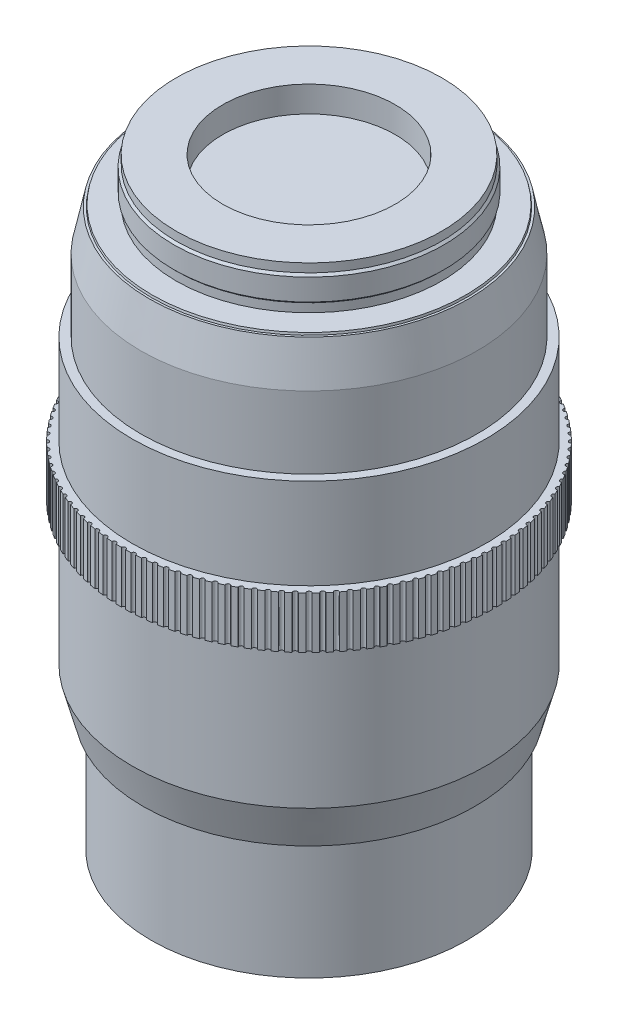
SolidWorks part; units mm, degrees
ref_plane "Front Plane" through (0, 0, 0) normal (0, 0, 1) x (1, 0, 0)
ref_plane "Top Plane" through (0, 0, 0) normal (0, 1, 0) x (1, 0, 0)
ref_plane "Right Plane" through (0, 0, 0) normal (1, 0, 0) x (0, 0, -1)
sketch "Sketch1" plane through (0, 0, 0) normal (1, 0, 0) x (0, 0, -1)
  line L0 (0, 0) -> (0, 75)
  line L1 (0, 75) -> (0, 80)
  line L2 (0, 87.5) -> (0, -12.5) construction
  line L3 (0, 80) -> (-15.4, 80)
  line L4 (-15.4, 80) -> (-15.4, 79)
  line L5 (-15.4, 79) -> (-15.65, 78.75)
  line L6 (-15.65, 78.75) -> (-15.65, 76.25)
  line L7 (-15.65, 76.25) -> (-15.4, 76)
  line L8 (-15.4, 76) -> (-15.4, 75)
  line L9 (-15.4, 75) -> (-18.1969, 75)
  line L10 (-18.1969, 75) -> (-18.25, 74.75)
  line L11 (-18.25, 74.75) -> (-18.5, 74.75)
  line L12 (-18.5, 74.75) -> (-19.5, 70.0454)
  line L13 (-19.5, 70.0454) -> (-19.5, 61.7)
  line L14 (-19.5, 61.7) -> (-20.5, 61.7)
  line L15 (-20.5, 61.7) -> (-20.5, 51.2)
  line L16 (-20.5, 51.2) -> (-21.5, 51.2)
  line L17 (-21.5, 51.2) -> (-21.5, 45.2)
  line L18 (-21.5, 45.2) -> (-20.5, 45.2)
  line L19 (-20.5, 45.2) -> (-20.5, 28.8651)
  line L20 (-20.5, 28.8651) -> (-19.25, 24.2)
  line L21 (-19.25, 24.2) -> (-18.3, 24.2)
  line L22 (-18.3, 24.2) -> (-18.3, 10.2728)
  line L23 (-18.3, 10.2728) -> (-16.7679, 9.2)
  line L24 (-16.7679, 9.2) -> (-16.0179, 9.2)
  line L25 (-16.0179, 9.2) -> (-16.0179, 8.7)
  line L26 (-16.0179, 8.7) -> (-8.9485, 3.75)
  line L27 (-8.9485, 3.75) -> (-8.6985, 3.75)
  line L28 (-8.6985, 3.75) -> (-8.6985, 3.5)
  line L29 (-8.6985, 3.5) -> (-3.7, 0)
  line L30 (-3.7, 0) -> (0, 0)
  point P8 (0, 37.5)
  point P9 (0, 37.5)
  point P51 (-18.775, 24.2)
  dimension "D1" = 75
  dimension "D2" = 5
  dimension "D3" = 100
  dimension "D4" = 7.4
  dimension "D5" = 35
  dimension "D6" = 3.5
  dimension "D7" = 0.25
  dimension "D8" = 0.25
  dimension "D9" = 9.2
  dimension "D10" = 0.75
  dimension "D11" = 0.5
  dimension "D12" = 36.6
  dimension "D13" = 38.5
  dimension "D14" = 15
  dimension "D15" = 15
  dimension "D16" = 41
  dimension "D17" = 21
  dimension "D18" = 43
  dimension "D19" = 6
  dimension "D20" = 10.5
  dimension "D21" = 5
  dimension "D22" = 30.8
  dimension "D23" = 0.25
  dimension "D24" = 0.25
  dimension "D25" = 1
  dimension "D26" = 1
  dimension "D27" = 39
  dimension "D28" = 37
  dimension "D29" = 12
  dimension "D30" = 0.25
  dimension "D31" = 0.25
revolve "Revolve1" add sketch "Sketch1" angle 360 about L2
cosmetic thread "Cosmetic Thread1" parameters "D2"=31.2
sketch "Sketch2" plane through (0, 80, 0) normal (0, 1, 0) x (1, 0, 0)
  circle A0 centre (0, 0) radius 10
  dimension "D1" = 20
extrude "Cut-Extrude1" cut sketch "Sketch2" against normal blind 3
ref_plane "WD" through (0, -2.8, 0) normal (0, -1, 0) x (-1, 0, 0)
ref_plane "Plane3" through (0, 45.2, 0) normal (0, -1, 0) x (-1, 0, 0)
ref_axis "Axis1" through (0, 45.2, 19.4351) along (0, 0, 1)
sketch "Sketch5" plane through (0, 45.2, 0) normal (0, -1, 0) x (-1, 0, 0)
  line L0 (0, -19.4351) -> (0, -22.1668) construction
  arc A1 (-0.25, -21.4985) -> (0.25, -21.4985) centre (0, -21.5) cw
  circle A2 centre (0, 0) radius 21.5 construction
  dimension "D1" = 0.25
extrude "Cut-Extrude2" cut sketch "Sketch5" against normal through all and the other way through all flip side to cut
pattern_circular "CirPattern9" count 120 every 3 about axis through (0, 87.5, 0) along (0, 1, 0) of "Cut-Extrude2"
